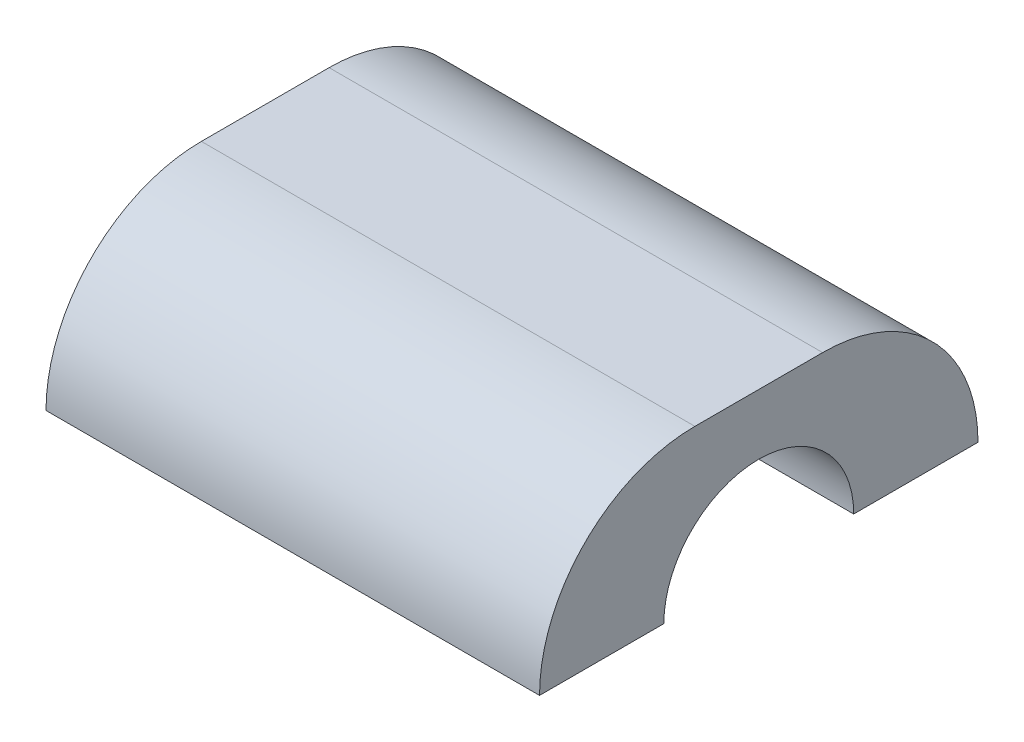
SolidWorks part; units mm, degrees
ref_plane "Front Plane" through (0, 0, 0) normal (0, 0, 1) x (1, 0, 0)
ref_plane "Top Plane" through (0, 0, 0) normal (0, 1, 0) x (1, 0, 0)
ref_plane "Right Plane" through (0, 0, 0) normal (1, 0, 0) x (0, 0, -1)
sketch "Sketch1" plane through (0, 0, 0) normal (0, 1, 0) x (1, 0, 0)
  line L1 (-35.0712, 32.4335) -> (22.1088, 32.4335)
  line L2 (-35.0712, 32.4335) -> (-35.0712, -18.3665)
  line L3 (-35.0712, -18.3665) -> (22.1088, -18.3665)
  line L4 (22.1088, 32.4335) -> (22.1088, -18.3665)
  line L5 (-35.0712, 32.4335) -> (22.1088, -18.3665) construction
  line L6 (-35.0712, -18.3665) -> (22.1088, 32.4335) construction
  point P0 (-6.4812, 7.0335)
  dimension "D1" = 50.8
  dimension "D2" = 57.18
extrude "Boss-Extrude1" add sketch "Sketch1" along normal blind 18
sketch "Sketch2" plane through (-35.0712, 0, 0) normal (-1, 0, 0) x (0, 0, 1)
  line L0 (-32.4335, 0) -> (18.3665, 0) construction
  circle A0 centre (-7.0335, 0) radius 11
  point P2 (-7.0335, 0)
extrude "Cut-Extrude1" cut sketch "Sketch2" against normal blind 58
fillet "Fillet2" radius 18 3 edges at (-6.4812, 18, 18.3665) (22.1088, 9, 18.3665) (-35.0712, 9, 18.3665)
fillet "Fillet3" radius 18 3 edges at (-35.0712, 9, -32.4335) (22.1088, 9, -32.4335) (-6.4812, 18, -32.4335)
